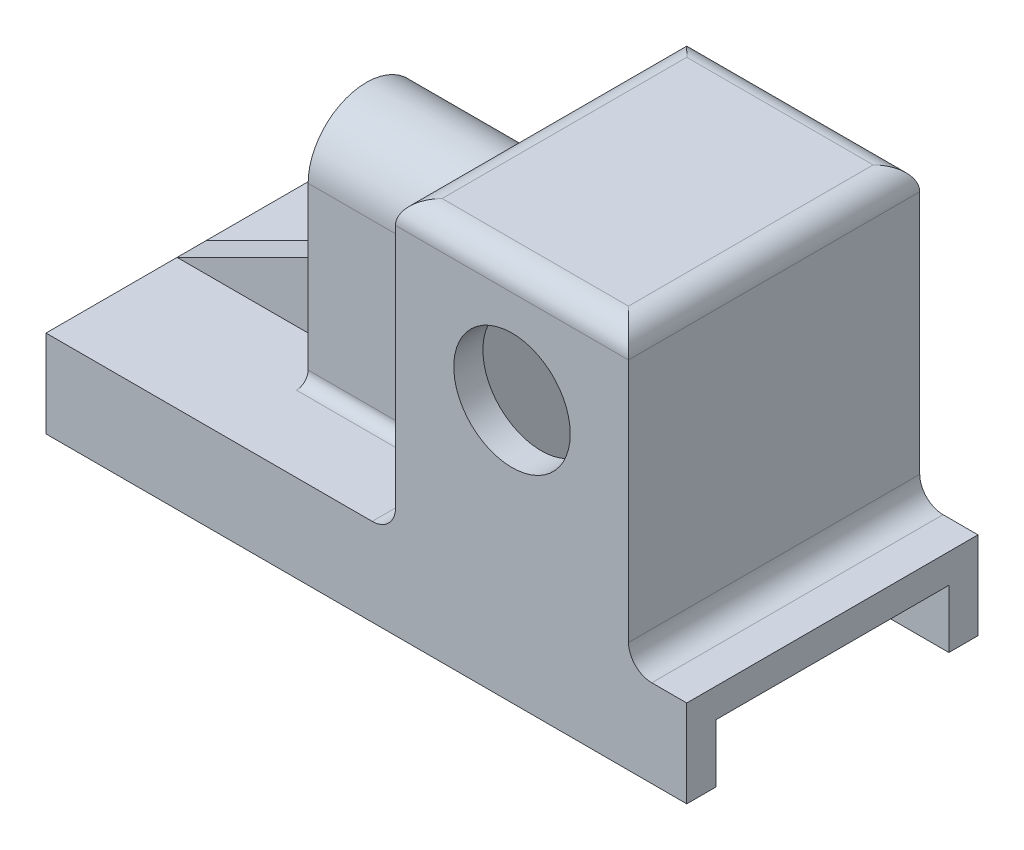
SolidWorks part; units mm, degrees
ref_plane "Front Plane" through (0, 0, 0) normal (0, 0, 1) x (1, 0, 0)
ref_plane "Top Plane" through (0, 0, 0) normal (0, 1, 0) x (1, 0, 0)
ref_plane "Right Plane" through (0, 0, 0) normal (1, 0, 0) x (0, 0, -1)
sketch "Sketch1" plane through (0, 0, 0) normal (0, 0, 1) x (1, 0, 0)
  line L0 (0, -10.0459) -> (0, 34.8165) construction
  line L1 (-55, 0) -> (55, 0)
  line L2 (-55, 0) -> (-55, 15)
  line L3 (-55, 15) -> (55, 15)
  line L4 (55, 0) -> (55, 15)
  dimension "D1" = 15
  dimension "D2" = 110
extrude "Boss-Extrude1" add sketch "Sketch1" along normal mid plane 50
sketch "Sketch2" plane through (55, 0, 0) normal (1, 0, 0) x (0, 0, -1)
  line L0 (-25, 0) -> (25, 0) construction
  line L1 (-20, 0) -> (20, 0)
  line L2 (-20, 0) -> (-20, 10)
  line L3 (-20, 10) -> (20, 10)
  line L4 (20, 0) -> (20, 10)
  line L5 (0, -2.2543) -> (0, 16.7805) construction
  dimension "D1" = 10
  dimension "D2" = 40
extrude "Cut-Extrude1" cut sketch "Sketch2" against normal through all
sketch "Sketch3" plane through (0, 0, 25) normal (0, 0, 1) x (1, 0, 0)
  line L0 (25, -3.7621) -> (25, 65) construction
  line L1 (55, 0) -> (55, 15) construction
  line L2 (5, 65) -> (45, 65)
  line L3 (45, 65) -> (45, 15)
  line L4 (55, 15) -> (-55, 15) construction
  line L5 (5, 65) -> (5, 15)
  line L6 (5, 15) -> (45, 15)
  line L7 (-55, 0) -> (55, 0) construction
  circle A0 centre (25, 45) radius 10
  dimension "D3" = 45
  dimension "D4" = 20
  dimension "D1" = 30
  dimension "D2" = 40
  dimension "D5" = 65
extrude "Boss-Extrude2" add sketch "Sketch3" against normal blind 50
fillet "Fillet1" radius 4 5 edges at (25, 65, -25) (25, 65, 25) (5, 65, 0) (45, 65, 0) (45, 15, 0)
sketch "Sketch5" plane through (0, 0, 0) normal (0, 0, 1) x (1, 0, 0)
  line L0 (25, -2.3334) -> (25, 68.1485) construction
  line L1 (9, 65) -> (41, 65) construction
  line L2 (10, 10) -> (40, 10)
  line L3 (10, 10) -> (10, 58)
  line L4 (12, 60) -> (38, 60)
  line L5 (40, 10) -> (40, 58)
  line L6 (-55, 0) -> (55, 0) construction
  arc A0 (38, 60) -> (40, 58) centre (38, 58) cw
  arc A1 (12, 60) -> (10, 58) centre (12, 58) ccw
  dimension "D3" = 2
  dimension "D1" = 30
  dimension "D2" = 5
  dimension "D4" = 10
extrude "Cut-Extrude2" cut sketch "Sketch5" against normal mid plane 40
fillet "Fillet2" radius 2 2 edges at (25, 60, 20) (25, 60, -20) tangent propagation no
sketch "Sketch6" plane through (5, 0, 0) normal (-1, 0, 0) x (0, 0, 1)
  line L0 (0, -1.8122) -> (0, 70.9009) construction
  line L1 (-25, 15) -> (25, 15) construction
  line L2 (-10, 15) -> (10, 15)
  line L3 (-10, 15) -> (-10, 44.7627)
  line L5 (10, 15) -> (10, 44.7627)
  arc A0 (10, 44.7627) -> (-10, 44.7627) centre (0, 44.7627) ccw
  dimension "D1" = 20
extrude "Boss-Extrude3" add sketch "Sketch6" along normal blind 30
sketch "Sketch7" plane through (0, 0, 0) normal (0, 0, 1) x (1, 0, 0)
  line L0 (-25, 30) -> (-55, 15)
  line L1 (-25, 15) -> (-25, 44.7627) construction
  dimension "D1" = 15
rib "Rib2" sketch "Sketch7" sketch "Sketch7" thickness 5 extrusion direction parallel to sketch draft on no parameters "D1"=5
fillet "Fillet3" radius 2 5 edges at (5, 29.8813, 10) (5, 29.8813, -10) (-10, 15, -10) (-10, 15, 10) (5, 54.7627, 0)
fillet "Fillet4" radius 4 4 edges at (4.4142, 15.5858, 10.5858) (4.4142, 15.5858, -10.5858) (5, 15, -18.5) (5, 15, 18.5)
hole_wizard "Tap Drill for M12x1.75 Tap1" positions "3DSketch2" profile "Sketch9" hole size "M12x1.75" standard "ANSI Metric"
sketch3d "3DSketch2"
  line L0 (-25, 44.7627, 0) -> (3, 44.7627, 0) construction
  point P0 (-25, 44.7627, 0)
sketch "Sketch9" plane through (-25, 44.7627, 0) normal (0, 1, 0) x (0, 0, 1)
  line L0 (0, 0) -> (0, 25.0644)
  line L1 (0, 25.0644) -> (5.1, 22)
  line L2 (5.1, 22) -> (5.1, 0)
  line L5 (5.1, 0) -> (0, 0)
  line L10 (0, 25.0644) -> (-5.1, 22) construction
  line L11 (0, -6.35) -> (0, 107.95) construction
  dimension "Hole Dia." = 10.2
  dimension "Hole Depth" = 22
  dimension "Drill Angle" = 118
cosmetic thread "Cosmetic Thread3" parameters "D1"=15, "D2"=12
fillet "Chamfer3" radius 1.6 1 edges at (-25, 44.7627, 5.1) type face fillet profile chamfer first side face at (-3, 44.7627, 5.1) second side face at (-25, 44.7627, 5.1)
